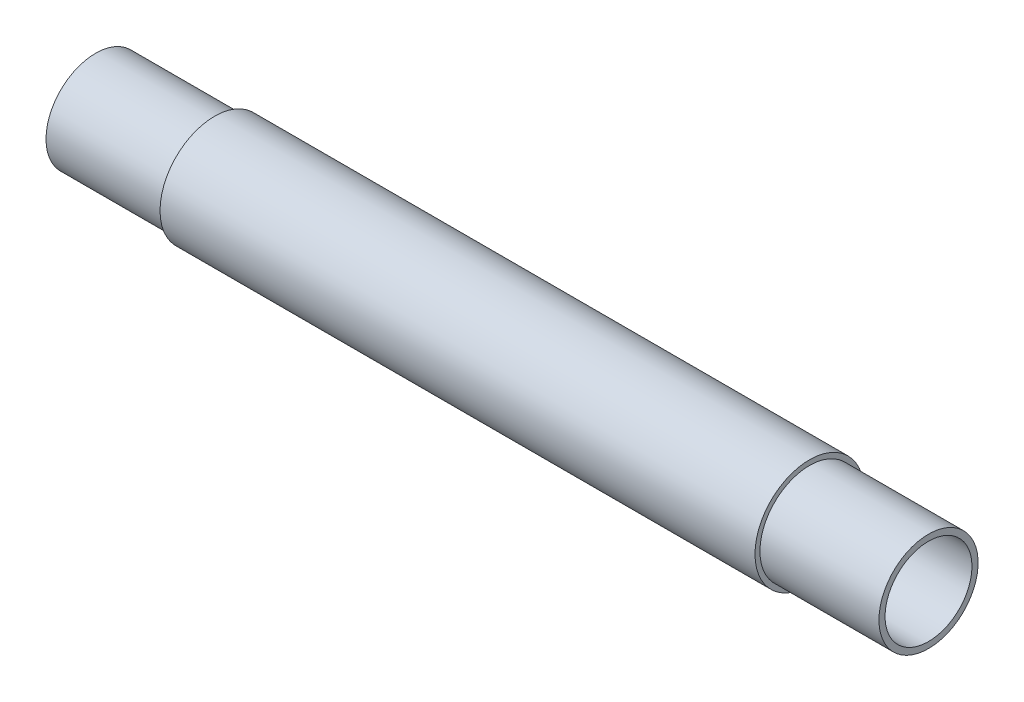
SolidWorks part; units mm, degrees
material "6061-T6 (SS)"
ref_plane "Front Plane" through (0, 0, 0) normal (0, 0, 1) x (1, 0, 0)
ref_plane "Top Plane" through (0, 0, 0) normal (0, 1, 0) x (1, 0, 0)
ref_plane "Right Plane" through (0, 0, 0) normal (1, 0, 0) x (0, 0, -1)
sketch "Sketch1" plane through (0, 0, 0) normal (0, 0, 1) x (1, 0, 0)
  line L0 (-92.3403, 0) -> (92.3403, 0) construction
  line L1 (0, 22.571) -> (0, -22.571) construction
  line L3 (0, 0) -> (76.2, 0)
  line L4 (0, 0) -> (0, 6.985)
  line L5 (0, 6.985) -> (76.2, 6.985)
  line L6 (76.2, 0) -> (76.2, 6.985)
  line L7 (0, 6.35) -> (-15.24, 6.35)
  line L8 (0, 6.35) -> (0, 0)
  line L9 (0, 0) -> (-15.24, 0)
  line L10 (-15.24, 6.35) -> (-15.24, 0)
  line L11 (76.2, 6.35) -> (91.44, 6.35)
  line L12 (76.2, 6.35) -> (76.2, 0)
  line L13 (76.2, 0) -> (91.44, 0)
  line L14 (91.44, 6.35) -> (91.44, 0)
  point P4 (0, 0)
  point P8 (0, 0)
  dimension "D1" = 76.2
  dimension "D2" = 6.985
  dimension "D3" = 15.24
  dimension "D4" = 15.24
  dimension "D5" = 6.35
  dimension "D6" = 6.35
revolve "Revolve1" add sketch "Sketch1" angle 360 about L0 region at (38.1, 3.4925, 0) region at (83.82, 3.175, 0)
sketch "Sketch2" plane through (91.44, 0, 0) normal (1, 0, 0) x (0, 0, -1)
  line L0 (-13.6292, 0) -> (13.6292, 0) construction
  line L1 (0, 9.0464) -> (0, -9.0464) construction
  circle A0 centre (0, 0) radius 5.5658
  point P5 (0, 0)
  point P9 (0, 0)
extrude "Cut-Extrude1" cut sketch "Sketch2" against normal up to surface (106.68 mm away) up to face at (-15.24, 0, 6.35)
ref_axis "Axis1" through (76.2, 0, 0) along (-1, 0, 0)
